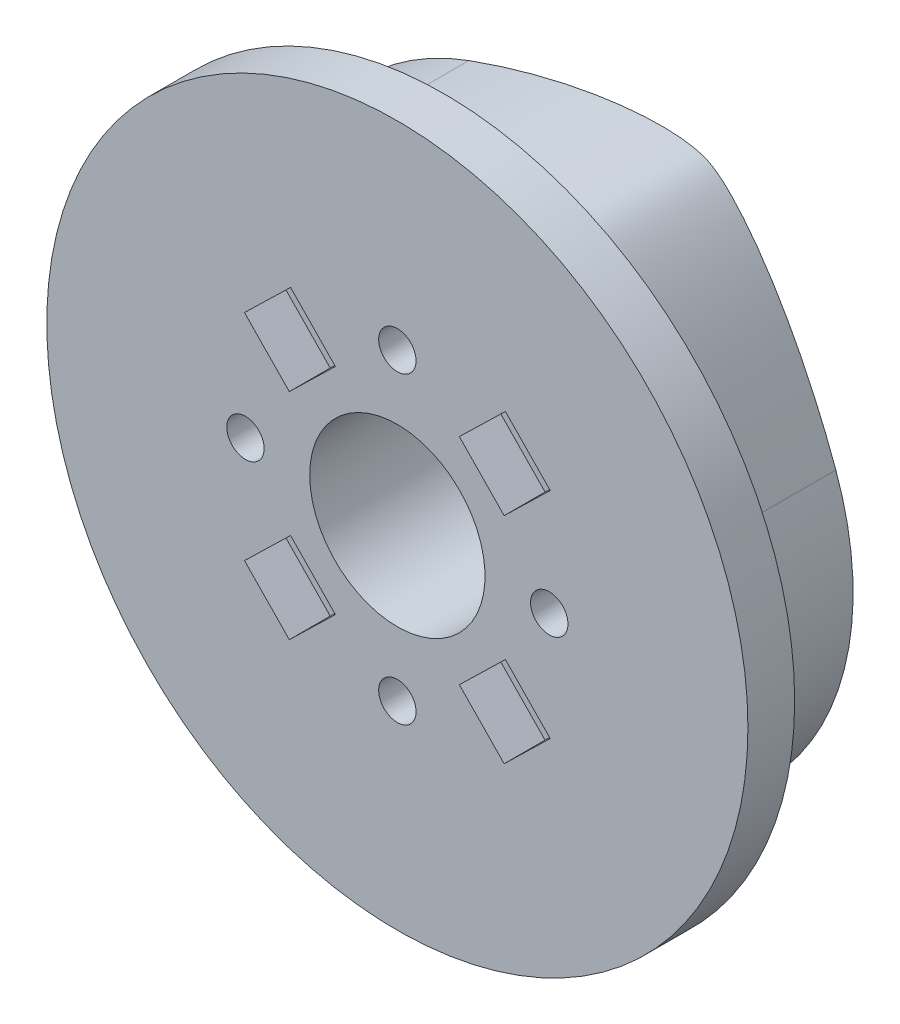
SolidWorks part; units mm, degrees
ref_plane "Front Plane" through (0, 0, 0) normal (1, 0, 0) x (0, 1, 0)
ref_plane "Top Plane" through (0, 0, 0) normal (0, 0, 1) x (0, 1, 0)
ref_plane "Right Plane" through (0, 0, 0) normal (0, 1, 0) x (-1, 0, 0)
sketch "Sketch1" plane through (0, 0, 0) normal (0, 0, 1) x (0, 1, 0)
  circle A0 centre (0, 0) radius 21
  circle A1 centre (0, 0) radius 13 construction
  circle A2 centre (0, 13) radius 1.6
  circle A3 centre (0, 13) radius 2.85
  circle A4 centre (13, 0) radius 2.85
  circle A5 centre (13, 0) radius 1.6
  circle A6 centre (0, -13) radius 2.85
  circle A7 centre (0, -13) radius 1.6
  circle A8 centre (-13, 0) radius 2.85
  circle A9 centre (-13, 0) radius 1.6
  point P19 (0, 0)
  dimension "D1" = 42
  dimension "D2" = 26
  dimension "D3" = 3.2
  dimension "D4" = 5.7
  dimension "D5" = 4
extrude "Boss-Extrude1" add sketch "Sketch1" along normal blind 10.5 contours A0 A8 A6 A4 A3 | A8 A9 | A3 A2 | A4 A5 | A6 A7 region at (0, 0, 0) region at (-13, -2.7694, 0) region at (0, 10.2306, 0) region at (13, -2.7694, 0) region at (0, -15.7694, 0)
sketch "Sketch2" plane through (0, 0, 0) normal (0, 0, -1) x (1, 0, 0)
  line L0 (0, 0) -> (0, 28.5) construction
  line L1 (0, 0) -> (12.0446, -25.8298) construction
  line L2 (0, 0) -> (-9.7476, -26.7812) construction
  line L3 (0, 0) -> (26.7812, -9.7476) construction
  line L4 (10.384, -26.6041) -> (-25.8683, -43.5089) construction
  line L5 (30.3658, -37.1246) -> (-82.3973, 3.9178) construction
  line L6 (37.1246, 30.3658) -> (-3.9178, -82.3973) construction
  circle A0 centre (0, 0) radius 28.5 construction
  circle A1 centre (0, 0) radius 24.5
  spline S0 degree 3 poles (-8.3795, -23.0225) (0.0777, -26.1007) (9.3995, -27.1075) (14.7237, -24.6248) (19.9443, -16.8367) (23.0225, -8.3795) knots 0 0 0 0 0.45 0.55 1 1 1 1
  circle M5 centre (0, 0) radius 21
  dimension "D1" = 57
  dimension "D2" = 49
  dimension "D6" = 20
  dimension "D7" = 30
  dimension "D8" = 30
  dimension "D3" = 155
  dimension "D4" = 45
  dimension "D5" = 45
  dimension "D9" = 90
  dimension "D10" = 90
  dimension "D11" = 90
extrude "Boss-Extrude3" add sketch "Sketch2" against normal up to surface (10.5 mm away) contours A1 M5 | A1 S0 region at (23.4454, 4.134, 0) region at (10.6154, 22.7398, 0) up to face at (21, 0, 10.5)
sketch "Sketch4" plane through (0, 0, 10.5) normal (0, 0, 1) x (1, 0, 0)
  circle A0 centre (0, 0) radius 30
  circle A5 centre (-13, 0) radius 1.6
  circle A6 centre (0, 13) radius 1.6
  circle A7 centre (13, 0) radius 1.6
  circle A8 centre (0, -13) radius 1.6
  dimension "D1" = 60
extrude "Boss-Extrude5" add sketch "Sketch4" along normal blind 4
sketch "Sketch3" plane through (0, 0, 0) normal (0, 0, -1) x (1, 0, 0)
  circle A0 centre (0, 0) radius 21
  circle A5 centre (-13, 0) radius 1.6
  circle A6 centre (0, 13) radius 1.6
  circle A7 centre (13, 0) radius 1.6
  circle A8 centre (0, -13) radius 1.6
  dimension "D1" = 42
extrude "Boss-Extrude4" add sketch "Sketch3" along normal blind 0.5
sketch "Sketch6" plane through (0, 0, -0.5) normal (0, 0, -1) x (1, 0, 0)
  line L0 (15.75, -2.75) -> (10.25, -2.75)
  line L1 (-2.75, 15.75) -> (2.75, 15.75)
  line L2 (-2.75, 15.75) -> (-2.75, 10.25)
  line L3 (-2.75, 10.25) -> (2.75, 10.25)
  line L4 (2.75, 15.75) -> (2.75, 10.25)
  line L5 (-2.75, 15.75) -> (2.75, 10.25) construction
  line L6 (-2.75, 10.25) -> (2.75, 15.75) construction
  line L7 (10.25, 2.75) -> (10.25, -2.75)
  line L8 (15.75, 2.75) -> (10.25, 2.75)
  line L9 (15.75, 2.75) -> (15.75, -2.75)
  line L10 (15.75, 2.75) -> (10.25, -2.75) construction
  line L11 (10.25, 2.75) -> (15.75, -2.75) construction
  line L12 (-2.75, -15.75) -> (-2.75, -10.25)
  line L13 (2.75, -10.25) -> (-2.75, -10.25)
  line L14 (2.75, -15.75) -> (2.75, -10.25)
  line L15 (2.75, -15.75) -> (-2.75, -15.75)
  line L16 (2.75, -15.75) -> (-2.75, -10.25) construction
  line L17 (2.75, -10.25) -> (-2.75, -15.75) construction
  line L18 (-15.75, 2.75) -> (-10.25, 2.75)
  line L19 (-10.25, -2.75) -> (-10.25, 2.75)
  line L20 (-15.75, -2.75) -> (-10.25, -2.75)
  line L21 (-15.75, -2.75) -> (-15.75, 2.75)
  line L22 (-15.75, -2.75) -> (-10.25, 2.75) construction
  line L23 (-10.25, -2.75) -> (-15.75, 2.75) construction
  point P0 (0, 13)
  point P21 (0, 0)
  dimension "D1" = 5.5
  dimension "D2" = 5.5
extrude "Cut-Extrude2" cut sketch "Sketch6" against normal offset from surface (3.5 mm away) 11.5 up to face at (14.6, 0, 14.5)
sketch "Sketch7" plane through (0, 0, 14.5) normal (0, 0, 1) x (1, 0, 0)
  line L0 (0, 0) -> (9.1924, 9.1924) construction
  line L1 (9.2456, 13.0807) -> (5.3041, 9.2465)
  line L2 (9.2456, 13.0807) -> (13.0807, 9.1383)
  line L3 (5.3041, 9.2465) -> (9.1392, 5.3041)
  line L4 (13.0807, 9.1383) -> (9.1392, 5.3041)
  line L5 (9.2456, 13.0807) -> (9.1392, 5.3041) construction
  line L6 (5.3041, 9.2465) -> (13.0807, 9.1383) construction
  line L7 (9.1383, -13.0807) -> (5.3041, -9.1392)
  line L8 (9.2465, -5.3041) -> (5.3041, -9.1392)
  line L9 (13.0807, -9.2456) -> (9.2465, -5.3041)
  line L10 (13.0807, -9.2456) -> (9.1383, -13.0807)
  line L11 (13.0807, -9.2456) -> (5.3041, -9.1392) construction
  line L12 (9.2465, -5.3041) -> (9.1383, -13.0807) construction
  line L13 (-13.0807, -9.1383) -> (-9.1392, -5.3041)
  line L14 (-5.3041, -9.2465) -> (-9.1392, -5.3041)
  line L15 (-9.2456, -13.0807) -> (-5.3041, -9.2465)
  line L16 (-9.2456, -13.0807) -> (-13.0807, -9.1383)
  line L17 (-9.2456, -13.0807) -> (-9.1392, -5.3041) construction
  line L18 (-5.3041, -9.2465) -> (-13.0807, -9.1383) construction
  line L19 (-9.1383, 13.0807) -> (-5.3041, 9.1392)
  line L20 (-9.2465, 5.3041) -> (-5.3041, 9.1392)
  line L21 (-13.0807, 9.2456) -> (-9.2465, 5.3041)
  line L22 (-13.0807, 9.2456) -> (-9.1383, 13.0807)
  line L23 (-13.0807, 9.2456) -> (-5.3041, 9.1392) construction
  line L24 (-9.2465, 5.3041) -> (-9.1383, 13.0807) construction
  circle A0 centre (0, 0) radius 13 construction
  circle A1 centre (9.1924, 9.1924) radius 1.6
  circle A10 centre (9.1924, -9.1924) radius 1.6
  circle A11 centre (-9.1924, -9.1924) radius 1.6
  circle A12 centre (-9.1924, 9.1924) radius 1.6
  point P18 (0, 0)
  point P34 (0, 0)
  dimension "D1" = 3.2
  dimension "D2" = 5.4988
  dimension "D3" = 5.5
extrude "Cut-Extrude3" cut sketch "Sketch7" against normal through all contours A1 | A12 | A11 | A10 region at (9.1924, 9.1924, 14.5) region at (9.1924, -9.1924, 14.5) region at (-9.1924, -9.1924, 14.5) region at (-9.1924, 9.1924, 14.5)
extrude "Cut-Extrude4" cut sketch "Sketch7<3>" against normal blind 3.5
sketch "Sketch7<3>" plane through (0, 0, 14.5) normal (0, 0, 1) x (1, 0, 0) same geometry as "Sketch7"
sketch "Sketch8" plane through (0, 0, -0.5) normal (0, 0, -1) x (1, 0, 0)
  circle A0 centre (0, 0) radius 7.5
  dimension "D1" = 15
extrude "Cut-Extrude5" cut sketch "Sketch8" against normal through all
